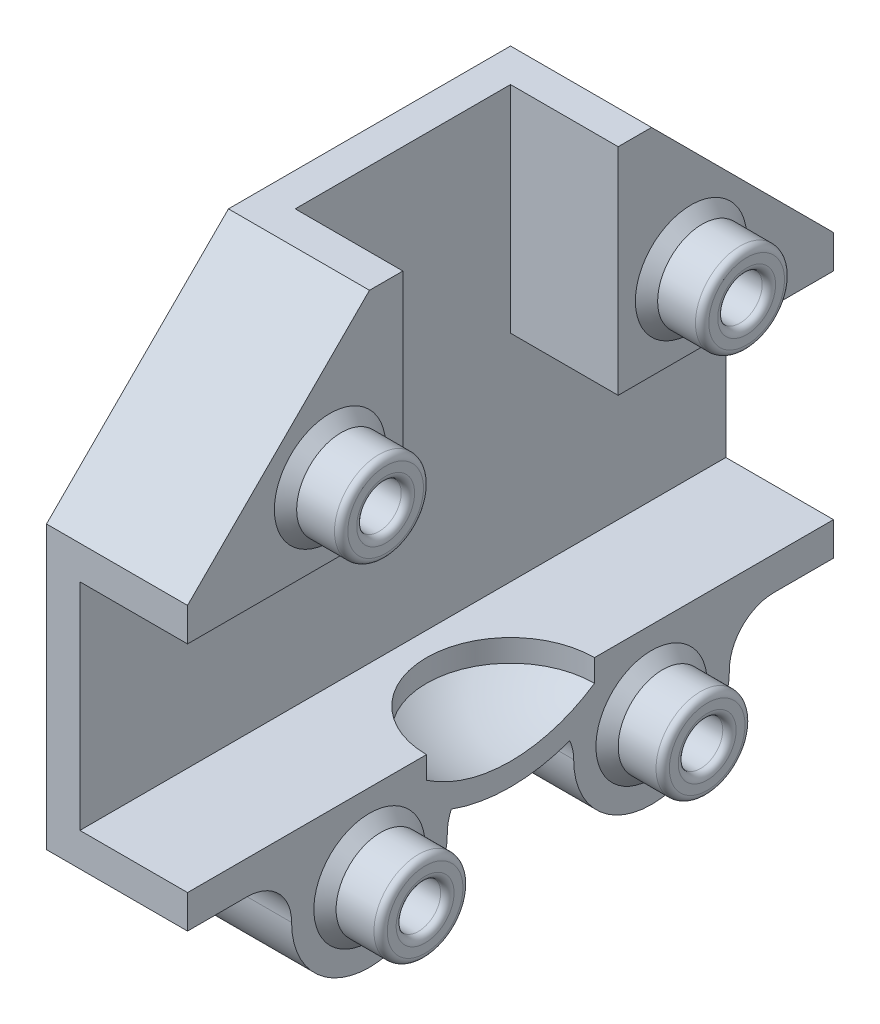
SolidWorks part; units mm, degrees
ref_plane "Front Plane" through (0, 0, 0) normal (0, 0, 1) x (1, 0, 0)
ref_plane "Top Plane" through (0, 0, 0) normal (0, 1, 0) x (1, 0, 0)
ref_plane "Right Plane" through (0, 0, 0) normal (1, 0, 0) x (0, 0, -1)
sketch "Sketch1" plane through (0, 0, 0) normal (1, 0, 0) x (0, 0, -1)
  line L0 (-29.025, 0) -> (29.025, 0) construction
  line L1 (0, 0) -> (0, 29.025) construction
  line L2 (-29.025, -9.675) -> (29.025, -9.675)
  line L3 (-9.675, 29.025) -> (-9.675, 9.675)
  line L4 (-9.675, 9.675) -> (-29.025, 9.675)
  line L5 (9.675, 29.025) -> (9.675, 9.675)
  line L6 (9.675, 9.675) -> (29.025, 9.675)
  line L7 (-9.675, 29.025) -> (9.675, 29.025) construction
  line L8 (-29.025, 9.675) -> (-29.025, -9.675) construction
  line L9 (29.025, 9.675) -> (29.025, -9.675) construction
  point P2 (0, 0)
  point P13 (0, 29.025)
  point P15 (-29.025, 0)
  point P17 (29.025, 0)
  dimension "D1" = 19.35
sketch "Sketch2" plane through (0, 0, 0) normal (1, 0, 0) x (0, 0, -1)
  line L0 (9.675, 29.025) -> (9.675, 9.675) construction
  line L1 (9.675, 9.675) -> (29.025, 9.675) construction
  line L2 (-9.675, 29.025) -> (-9.675, 9.675) construction
  line L3 (-9.675, 9.675) -> (-29.025, 9.675) construction
  line L4 (-29.025, -9.675) -> (29.025, -9.675) construction
  line L5 (9.675, 29.025) -> (9.675, 9.675) construction
  line L6 (9.675, 9.675) -> (29.025, 9.675) construction
  line L7 (-9.675, 29.025) -> (-9.675, 9.675) construction
  line L8 (-9.675, 9.675) -> (-29.025, 9.675) construction
  line L9 (-29.025, -9.675) -> (29.025, -9.675) construction
  line L10 (-12.675, 29.025) -> (-12.675, 12.675) construction
  line L11 (-12.675, 12.675) -> (-29.025, 12.675) construction
  line L12 (12.675, 29.025) -> (12.675, 12.675) construction
  line L13 (12.675, 12.675) -> (29.025, 12.675) construction
  line L14 (-29.025, -12.675) -> (29.025, -12.675) construction
  line L15 (-29.025, 9.675) -> (-29.025, 12.675)
  line L16 (-29.025, 12.675) -> (-12.675, 29.025)
  line L17 (-12.675, 29.025) -> (-9.675, 29.025)
  line L18 (-9.675, 29.025) -> (-9.675, 9.675)
  line L19 (-9.675, 9.675) -> (-29.025, 9.675)
  line L20 (-29.025, -9.675) -> (-29.025, -12.675)
  line L21 (-29.025, -12.675) -> (29.025, -12.675)
  line L22 (29.025, -12.675) -> (29.025, -9.675)
  line L23 (29.025, -9.675) -> (-29.025, -9.675)
  line L24 (9.675, 29.025) -> (12.675, 29.025)
  line L25 (12.675, 29.025) -> (29.025, 12.675)
  line L26 (29.025, 12.675) -> (29.025, 9.675)
  line L27 (29.025, 9.675) -> (9.675, 9.675)
  line L28 (9.675, 9.675) -> (9.675, 29.025)
  dimension "D1" = 3
  dimension "D2" = 3
  dimension "D3" = 3
extrude "Boss-Extrude1" add sketch "Sketch2" against normal blind 9.675
sketch "Sketch3" plane through (-9.675, 0, 0) normal (-1, 0, 0) x (0, 0, 1)
  line L0 (-29.025, 12.675) -> (-12.675, 29.025)
  line L1 (-12.675, 29.025) -> (12.675, 29.025)
  line L2 (12.675, 29.025) -> (29.025, 12.675)
  line L3 (29.025, 12.675) -> (29.025, -12.675)
  line L4 (29.025, -12.675) -> (-29.025, -12.675)
  line L5 (-29.025, -12.675) -> (-29.025, 12.675)
extrude "Boss-Extrude2" add sketch "Sketch3" along normal blind 3
sketch "Sketch4" plane through (0, 0, 0) normal (1, 0, 0) x (0, 0, -1)
  line L0 (-12.675, -16.675) -> (12.675, -16.675) construction
  line L1 (12.675, -16.675) -> (29.025, -16.675) construction
  line L2 (-12.675, -16.675) -> (-29.025, -16.675) construction
  line L3 (-29.025, -9.675) -> (-29.025, 9.675) construction
  line L4 (29.025, 9.675) -> (29.025, -9.675) construction
  line L7 (29.025, -9.675) -> (-29.025, -9.675) construction
  circle A0 centre (-12.675, -16.675) radius 5
  circle A1 centre (12.675, -16.675) radius 5
  circle A2 centre (-12.675, -16.675) radius 7
  circle A3 centre (12.675, -16.675) radius 7
  dimension "D1" = 10
  dimension "D2" = 2
sketch "Sketch5" plane through (0, 0, 0) normal (1, 0, 0) x (0, 0, -1)
  line L0 (-12.675, -16.675) -> (-29.025, -16.675) construction
  line L1 (12.675, -16.675) -> (29.025, -16.675) construction
  line L2 (-29.025, -12.675) -> (29.025, -12.675) construction
  line L3 (-29.025, -12.675) -> (-23.675, -12.675)
  line L4 (29.025, -9.675) -> (-29.025, -9.675) construction
  line L5 (29.025, -9.675) -> (-29.025, -9.675)
  line L6 (-29.025, -9.675) -> (-29.025, -12.675)
  line L7 (29.025, -9.675) -> (29.025, -12.675)
  line L8 (-1.675, -12.675) -> (1.675, -12.675)
  line L9 (23.675, -12.675) -> (29.025, -12.675)
  circle A0 centre (12.675, -16.675) radius 7 construction
  circle A1 centre (-12.675, -16.675) radius 7 construction
  arc A2 (5.675, -16.675) -> (19.675, -16.675) centre (12.675, -16.675) ccw
  arc A3 (-19.675, -16.675) -> (-5.675, -16.675) centre (-12.675, -16.675) ccw
  arc A4 (-19.675, -16.675) -> (-23.675, -12.675) centre (-23.675, -16.675) ccw
  arc A5 (23.675, -12.675) -> (19.675, -16.675) centre (23.675, -16.675) ccw
  arc A6 (-1.675, -12.675) -> (-5.675, -16.675) centre (-1.675, -16.675) ccw
  arc A7 (5.675, -16.675) -> (1.675, -12.675) centre (1.675, -16.675) ccw
extrude "Boss-Extrude3" add sketch "Sketch5" against normal up to surface (12.675 mm away) up to face at (-12.675, 9.675, 0)
sketch "Sketch6" plane through (0, 0, 0) normal (1, 0, 0) x (0, 0, -1)
  line L0 (-16.2212, 16.2212) -> (-20.85, 20.85) construction
  line L2 (-12.675, 29.025) -> (-29.025, 12.675) construction
  line L4 (-16.2212, 16.2212) -> (-9.675, 16.2212) construction
  line L6 (-9.675, 9.675) -> (-9.675, 29.025) construction
  line L8 (-16.2212, 16.2212) -> (-16.2212, 9.675) construction
  line L9 (-29.025, 9.675) -> (-9.675, 9.675) construction
  line L10 (0, 0) -> (0, 29.025) construction
  line L11 (-9.675, 29.025) -> (9.675, 29.025) construction
  circle A0 centre (-12.675, -16.675) radius 2
  circle A1 centre (12.675, -16.675) radius 2
  circle A3 centre (-16.2212, 16.2212) radius 5 construction
  circle A4 centre (-16.2212, 16.2212) radius 2
  circle A5 centre (16.2212, 16.2212) radius 2
  dimension "D1" = 10
  dimension "D2" = 4
extrude "Cut-Extrude1" cut sketch "Sketch6" against normal through all
sketch "Sketch7" plane through (-12.675, 0, 0) normal (-1, 0, 0) x (0, 0, 1)
  circle A0 centre (-16.2212, 16.2212) radius 3
  circle A1 centre (16.2212, 16.2212) radius 3
  circle A2 centre (-12.675, -16.675) radius 3
  circle A3 centre (12.675, -16.675) radius 3
  dimension "D1" = 6
extrude "Cut-Extrude3" cut sketch "Sketch7" against normal offset from surface (11.175 mm away) 1.5 up to face at (0, 16.2212, -14.2212)
sketch "Sketch8" plane through (0, 0, 0) normal (1, 0, 0) x (0, 0, -1)
  circle A0 centre (-16.2212, 16.2212) radius 4
  circle A1 centre (16.2212, 16.2212) radius 4
  circle A2 centre (12.675, -16.675) radius 4
  circle A3 centre (-12.675, -16.675) radius 4
  arc A4 (-19.675, -16.675) -> (-5.675, -16.675) centre (-12.675, -16.675) ccw construction
  circle A10 centre (-16.2212, 16.2212) radius 2
  circle A11 centre (-16.2212, 16.2212) radius 2
  circle A12 centre (12.675, -16.675) radius 2
  circle A13 centre (12.675, -16.675) radius 2
  circle A14 centre (-12.675, -16.675) radius 2
  circle A15 centre (-12.675, -16.675) radius 2
  circle A16 centre (16.2212, 16.2212) radius 2
  circle A17 centre (16.2212, 16.2212) radius 2
  dimension "D1" = 3
  dimension "D2" = 0
  dimension "D3" = 0
  dimension "D4" = 0
  dimension "D5" = 0
extrude "Boss-Extrude4" add sketch "Sketch8" along normal blind 5
chamfer "Chamfer1" distance 1 4 edges at (0, -16.675, -16.675) (0, -16.675, 8.675) (0, 16.2212, -12.2212) (0, 16.2212, 20.2212)
fillet "Fillet1" radius 0.6 8 edges at (5, -16.675, 10.675) (5, -16.675, 8.675) (5, -16.675, -16.675) (5, -16.675, -14.675) (5, 16.2212, -18.2212) (5, 16.2212, -20.2212) (5, 16.2212, 14.2212) (5, 16.2212, 12.2212)
sketch "Sketch10" plane through (0, -9.675, 0) normal (0, 1, 0) x (1, 0, 0)
  circle A0 centre (0, 0) radius 7.55
  dimension "D1" = 15.1
extrude "Cut-Extrude4" cut sketch "Sketch10" against normal blind 2
sketch "Sketch11" plane through (0, 0, 0) normal (1, 0, 0) x (0, 0, -1)
  line L0 (0, -11.675) -> (0, -15.975)
  line L1 (7.55, -11.675) -> (-7.55, -11.675) construction
  line L2 (0, -11.675) -> (10.7317, -11.675)
  line L5 (0, -11.675) -> (0, -13.975) construction
  line L6 (0, -11.675) -> (7.55, -11.675) construction
  line L7 (-2, -9.675) -> (12.4955, -9.675) construction
  line L8 (-2, -9.675) -> (-2, -15.8458) construction
  arc A0 (0, -13.975) -> (7.55, -11.675) centre (0, -0.4332) ccw construction
  arc A1 (0, -15.975) -> (10.7317, -11.675) centre (0, -0.4332) ccw
  arc A2 (-2, -15.8458) -> (12.4955, -9.675) centre (0, -0.4332) ccw construction
  dimension "D1" = 2.3
  dimension "D2" = 2
revolve "Revolve1" add sketch "Sketch11" angle 180 about L0 reverse direction yes
sketch "Sketch12" plane through (0, 0, 0) normal (1, 0, 0) x (0, 0, -1)
  line L0 (0, -13.975) -> (0, -11.675)
  line L1 (7.55, -11.675) -> (-7.55, -11.675) construction
  line L2 (0, -11.675) -> (7.55, -11.675)
  arc A0 (0, -13.975) -> (7.55, -11.675) centre (0, -0.4332) ccw construction
  arc A1 (0, -13.975) -> (7.55, -11.675) centre (0, -0.4332) ccw
revolve "Cut-Revolve1" cut sketch "Sketch12" angle 360 about L0
